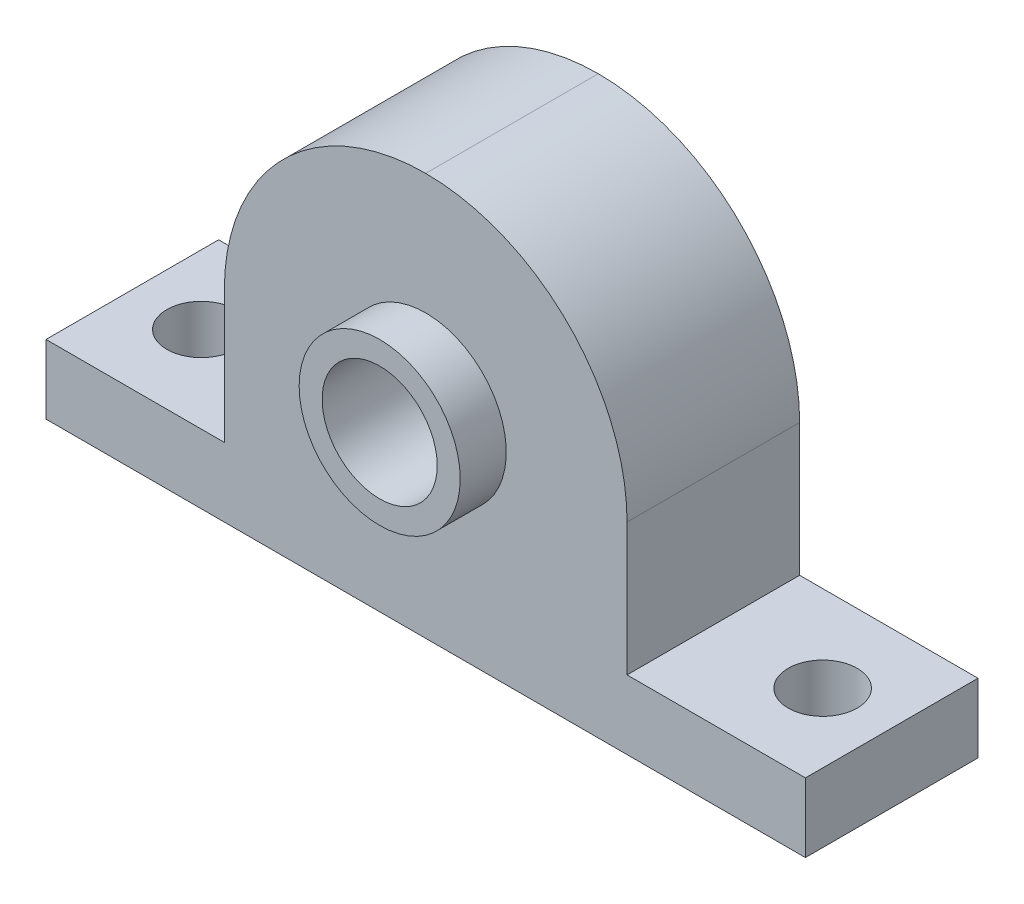
SolidWorks part; units mm, degrees
ref_plane "Front Plane" through (0, 0, 0) normal (0, 0, 1) x (1, 0, 0)
ref_plane "Top Plane" through (0, 0, 0) normal (0, 1, 0) x (1, 0, 0)
ref_plane "Right Plane" through (0, 0, 0) normal (1, 0, 0) x (0, 0, -1)
sketch "Sketch1" plane through (0, 0, 0) normal (0, 1, 0) x (1, 0, 0)
  line L1 (-33, -7.5) -> (33, -7.5)
  line L2 (-33, -7.5) -> (-33, 7.5)
  line L3 (-33, 7.5) -> (33, 7.5)
  line L4 (33, -7.5) -> (33, 7.5)
  line L5 (-33, -7.5) -> (33, 7.5) construction
  line L6 (-33, 7.5) -> (33, -7.5) construction
  point P0 (0, 0)
  dimension "D1" = 66
  dimension "D2" = 15
extrude "Boss-Extrude1" add sketch "Sketch1" along normal blind 6
sketch "Sketch2" plane through (0, 6, 0) normal (0, 1, 0) x (1, 0, 0)
  line L0 (33, 7.5) -> (-33, 7.5) construction
  line L1 (-17.5, -7.5) -> (17.5, -7.5)
  line L2 (-17.5, -7.5) -> (-17.5, 7.5)
  line L3 (-17.5, 7.5) -> (17.5, 7.5)
  line L4 (17.5, -7.5) -> (17.5, 7.5)
  line L5 (-17.5, -7.5) -> (17.5, 7.5) construction
  line L6 (-17.5, 7.5) -> (17.5, -7.5) construction
  point P0 (0, 0)
  dimension "D1" = 35
extrude "Boss-Extrude2" add sketch "Sketch2" along normal blind 29
fillet "Fillet1" radius 17.5 2 edges at (17.5, 35, 0) (-17.5, 35, 0)
sketch "Sketch3" plane through (0, 0, 7.5) normal (0, 0, 1) x (1, 0, 0)
  circle A0 centre (0, 17.5) radius 7
  arc A2 (17.5, 17.5) -> (0, 35) centre (0, 17.5) ccw construction
  dimension "D1" = 14
extrude "Boss-Extrude3" add sketch "Sketch3" along normal blind 4
sketch "Sketch4" plane through (0, 0, 11.5) normal (0, 0, 1) x (1, 0, 0)
  circle A0 centre (0, 17.5) radius 5
  dimension "D1" = 10
extrude "Cut-Extrude1" cut sketch "Sketch4" against normal through all
sketch "Sketch5" plane through (0, 6, 0) normal (0, 1, 0) x (1, 0, 0)
  line L0 (-33, 7.5) -> (-33, -7.5) construction
  circle A0 centre (-27, 0) radius 3
  dimension "D1" = 6
  dimension "D2" = 6
extrude "Cut-Extrude2" cut sketch "Sketch5" against normal through all
mirror "Mirror1" about plane through (0, 0, 0) normal (1, 0, 0) of "Cut-Extrude2"
